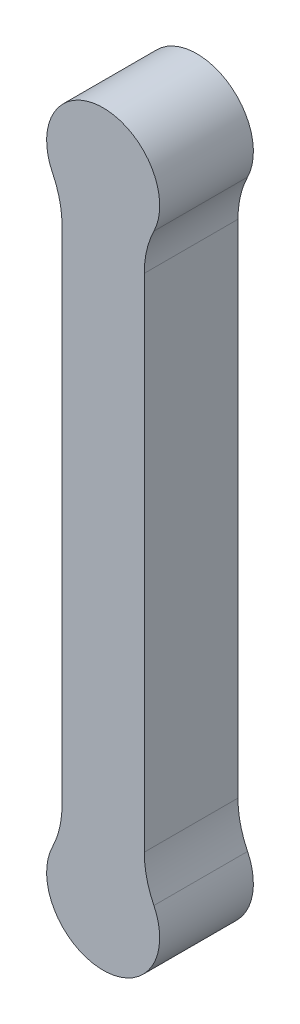
SolidWorks part; units mm, degrees
ref_plane "Plan de face" through (0, 0, 0) normal (0, 0, 1) x (1, 0, 0)
ref_plane "Plan de dessus" through (0, 0, 0) normal (0, 1, 0) x (1, 0, 0)
ref_plane "Plan de droite" through (0, 0, 0) normal (1, 0, 0) x (0, 0, -1)
sketch "Esquisse1" plane through (0, 0, 0) normal (0, 0, 1) x (1, 0, 0)
  line L0 (0, 40.1284) -> (0, 27.801) construction
  line L1 (-4.3873, 29.6918) -> (-4.3873, -29.6918)
  line L2 (-1.5343, 0) -> (1.2311, 0) construction
  line L3 (4.3873, 29.6918) -> (4.3873, -29.6918)
  line L4 (0, 0) -> (0, -27.801) construction
  line L5 (0, -39.8716) -> (0, -41.6693) construction
  arc A0 (-4.3873, -29.6918) -> (4.3873, -29.6918) centre (0, -33.8363) ccw
  arc A1 (-4.3873, 29.6918) -> (4.3873, 29.6918) centre (0, 33.8363) cw
  dimension "D1" = 80
extrude "Boss.-Extru.1" add sketch "Esquisse1" along normal blind 10
fillet "Congé1" radius 10 4 edges at (-4.3873, -29.6918, 5) (-4.3873, 29.6918, 5) (4.3873, -29.6918, 5) (4.3873, 29.6918, 5)
equation "\"L1\"= 80mm"
equation "\"D1@Esquisse1\"=\"L1\""
